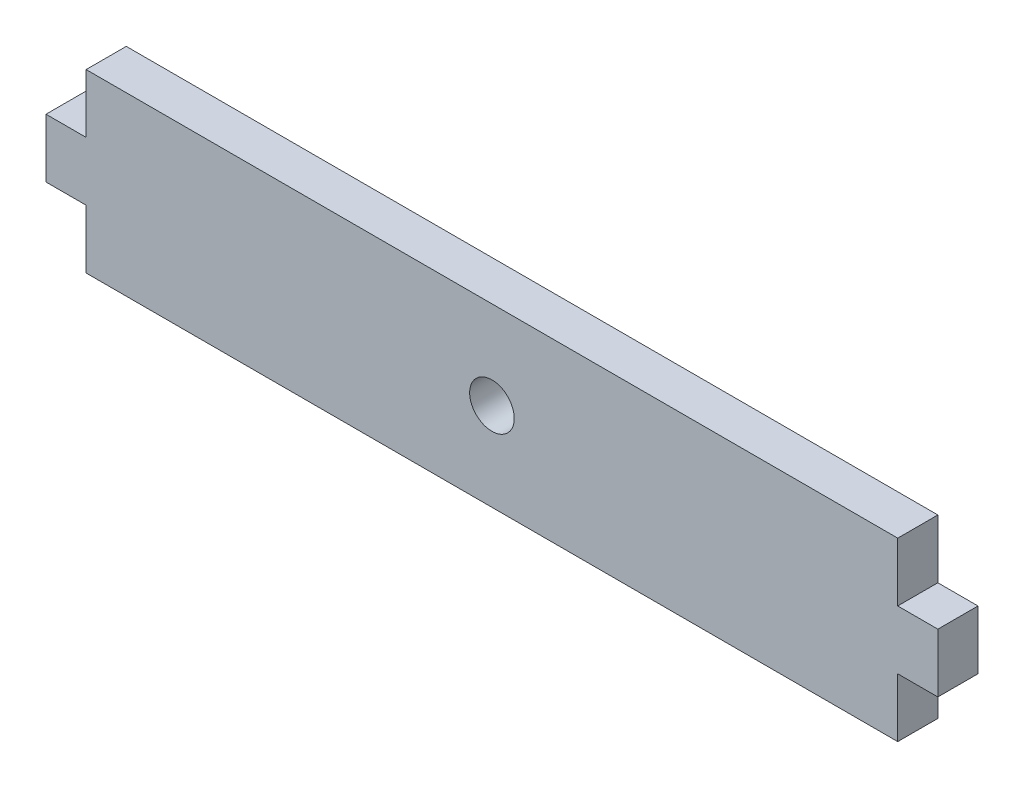
SolidWorks part; units mm, degrees
ref_plane "Front Plane" through (0, 0, 0) normal (0, 0, 1) x (1, 0, 0)
ref_plane "Top Plane" through (0, 0, 0) normal (0, 1, 0) x (1, 0, 0)
ref_plane "Right Plane" through (0, 0, 0) normal (1, 0, 0) x (0, 0, -1)
sketch "Sketch1" plane through (0, 0, 0) normal (0, 0, 1) x (1, 0, 0)
  line L0 (0, 8.718) -> (100, 8.718) construction
  line L1 (4.5, -1.1624) -> (95.5, -1.1624)
  line L2 (0, 5.4246) -> (0, 12.0115)
  line L3 (4.5, 18.5985) -> (95.5, 18.5985)
  line L4 (100, 5.4246) -> (100, 12.0115)
  line L6 (50, 18.5985) -> (50, -1.1624) construction
  line L7 (0, 12.0115) -> (4.5, 12.0115)
  line L8 (4.5, 18.5985) -> (4.5, 12.0115)
  line L11 (0, 5.4246) -> (4.5, 5.4246)
  line L12 (4.5, -1.1624) -> (4.5, 5.4246)
  line L15 (100, 12.0115) -> (95.5, 12.0115)
  line L16 (95.5, 18.5985) -> (95.5, 12.0115)
  line L19 (100, 5.4246) -> (95.5, 5.4246)
  line L20 (95.5, -1.1624) -> (95.5, 5.4246)
  circle A0 centre (50, 8.718) radius 2.5
  point P17 (50, 8.718)
  dimension "D3" = 5
  dimension "D1" = 100
  dimension "D2" = 4.5
extrude "Boss-Extrude1" add sketch "Sketch1" along normal blind 4.5
equation "\"D2@Sketch1\" = \"mdf@fmv1.assembly\""
equation "\"D1@Boss-Extrude1\"=\"mdf@fmv1.assembly\""
